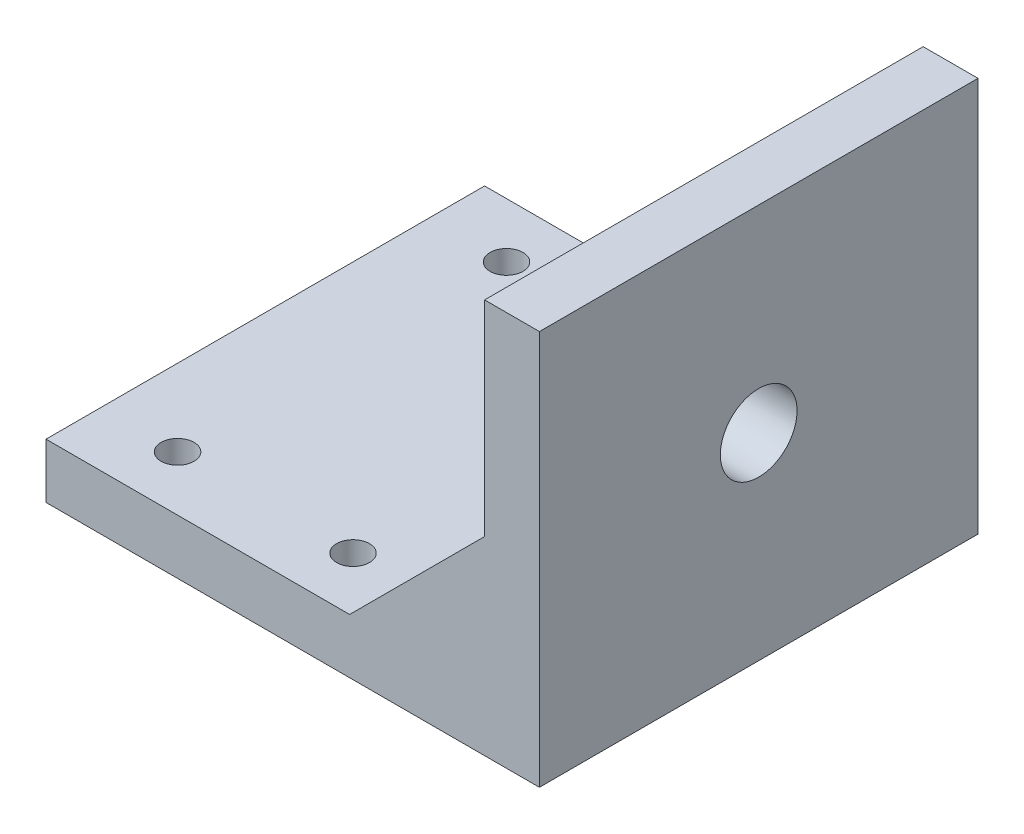
SolidWorks part; units mm, degrees
material "5454-H32"
ref_plane "Alzado" through (0, 0, 0) normal (0, 0, 1) x (1, 0, 0)
ref_plane "Planta" through (0, 0, 0) normal (0, 1, 0) x (1, 0, 0)
ref_plane "Vista lateral" through (0, 0, 0) normal (1, 0, 0) x (0, 0, -1)
sketch "Croquis1" plane through (0, 0, 0) normal (0, 0, 1) x (1, 0, 0)
  line L0 (0.5514, 34.1831) -> (0.5514, -1.8169)
  line L1 (0.5514, 34.1831) -> (-4.4486, 34.1831)
  line L2 (-4.4486, 34.1831) -> (-4.4486, 3.1831)
  line L3 (-4.4486, 3.1831) -> (-44.4486, 3.1831)
  line L4 (-44.4486, 3.1831) -> (-44.4486, -1.8169)
  line L5 (-44.4486, -1.8169) -> (0.5514, -1.8169)
  dimension "D1" = 5
  dimension "D2" = 36
  dimension "D3" = 45
extrude "Saliente-Extruir1" add sketch "Croquis1" along normal blind 40
sketch "Croquis2" plane through (0.5514, 0, 0) normal (1, 0, 0) x (0, 0, -1)
  line L0 (-40, 34.1831) -> (0, -1.8169) construction
  circle A0 centre (-20, 16.1831) radius 3.5
  dimension "D1" = 7
extrude "Cortar-Extruir1" cut sketch "Croquis2" against normal through all
sketch "Croquis3" plane through (0, 0, 40) normal (0, 0, 1) x (1, 0, 0)
  line L0 (-4.4486, 15.491) -> (-16.7565, 3.1831)
  line L3 (-4.4486, 34.1831) -> (-4.4486, 3.1831) construction
  line L4 (-4.4486, 3.1831) -> (-44.4486, 3.1831) construction
  line L5 (-16.7565, 3.1831) -> (-4.4486, 3.1831)
  line L6 (-4.4486, 3.1831) -> (-4.4486, 15.491)
  dimension "D1" = 45
  dimension "D2" = 12.3079
extrude "Saliente-Extruir2" add sketch "Croquis3" against normal blind 7
sketch "Croquis4" plane through (0, 0, 0) normal (0, 0, -1) x (-1, 0, 0)
  line L0 (4.4486, 3.1831) -> (16.7565, 3.1831)
  line L1 (16.7565, 3.1831) -> (4.4486, 15.491)
  line L2 (4.4486, 15.491) -> (4.4486, 3.1831)
extrude "Saliente-Extruir3" add sketch "Croquis4" against normal blind 7
sketch "Croquis5" plane through (0, -1.8169, 0) normal (0, -1, 0) x (1, 0, 0)
  line L2 (-44.4486, 40) -> (-44.4486, 0) construction
  line L3 (-44.4486, 40) -> (0.5514, 40) construction
  line L4 (-44.4486, 20) -> (0.5514, 20) construction
  line L5 (0.5514, 40) -> (0.5514, 0) construction
  circle A4 centre (-37.4486, 35) radius 1.5
  circle A6 centre (-21.4486, 35) radius 1.5
  circle A7 centre (-21.4486, 5) radius 1.5
  circle A8 centre (-37.4486, 5) radius 1.5
  dimension "D1" = 3
  dimension "D2" = 7
  dimension "D4" = 22
  dimension "D5" = 5
  dimension "D3" = 5
extrude "Cortar-Extruir2" cut sketch "Croquis5" against normal through all
